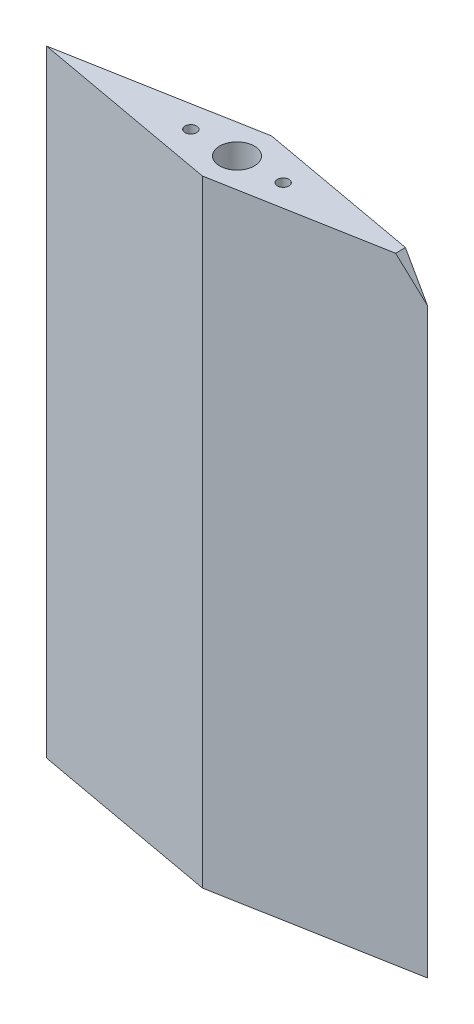
SolidWorks part; units mm, degrees
ref_plane "Front Plane" through (0, 0, 0) normal (0, 0, 1) x (1, 0, 0)
ref_plane "Top Plane" through (0, 0, 0) normal (0, 1, 0) x (1, 0, 0)
ref_plane "Right Plane" through (0, 0, 0) normal (1, 0, 0) x (0, 0, -1)
sketch "Sketch1" plane through (0, 0, 0) normal (0, 0, 1) x (1, 0, 0)
  line L0 (101.7924, 735.6565) -> (49.4049, 673.5573)
  line L1 (49.4049, 673.5573) -> (49.4049, 396.4974)
  line L2 (49.4049, 396.4974) -> (154.1799, 396.4974)
  line L3 (154.1799, 396.4974) -> (154.1799, 556.6364)
  line L4 (154.1799, 673.5573) -> (101.7924, 735.6565)
  line L5 (154.1799, 673.5573) -> (128.876, 673.5573)
  line L6 (128.876, 673.5573) -> (151.1488, 645.2298)
  line L7 (151.1488, 645.2298) -> (129.452, 645.2298)
  line L8 (129.452, 645.2298) -> (151.1488, 617.6349)
  line L9 (151.1488, 617.6349) -> (128.684, 617.6349)
  line L10 (128.684, 617.6349) -> (151.1488, 589.0632)
  line L11 (151.1488, 589.0632) -> (128.684, 589.0632)
  line L12 (128.684, 589.0632) -> (154.1799, 556.6364)
  point P2 (101.7924, 396.4974)
  dimension "D1" = 104.775
extrude "Boss-Extrude1" add sketch "Sketch1" along normal blind 9.525 and the other way blind 9.525
sketch "Sketch2" plane through (0, 396.4974, 0) normal (0, -1, 0) x (-1, 0, 0)
  line L0 (-49.4049, 0) -> (-101.7924, -9.525)
  line L1 (-49.4049, 9.525) -> (-49.4049, -9.525) construction
  line L2 (-49.4049, -9.525) -> (-154.1799, -9.525) construction
  line L3 (-101.7924, -9.525) -> (-154.1799, 0)
  line L4 (-154.1799, 9.525) -> (-154.1799, -9.525) construction
  line L5 (-154.1799, 0) -> (-159.6573, 0)
  line L6 (-159.6573, 0) -> (-159.6573, -13.6491)
  line L7 (-159.6573, -13.6491) -> (-44.1585, -13.6491)
  line L8 (-44.1585, -13.6491) -> (-44.1585, 0)
  line L9 (-44.1585, 0) -> (-49.4049, 0)
extrude "Cut-Extrude1" cut sketch "Sketch2" against normal through all
sketch "Sketch3" plane through (0, 396.4974, 0) normal (0, -1, 0) x (1, 0, 0)
  line L0 (49.4049, 0) -> (101.7924, -9.525)
  line L1 (101.7924, -9.525) -> (154.1799, 0)
  line L2 (154.1799, 0) -> (159.5806, 0)
  line L3 (159.5806, 0) -> (159.5806, -14.5007)
  line L4 (159.5806, -14.5007) -> (43.682, -14.5007)
  line L5 (43.682, -14.5007) -> (43.682, 0)
  line L6 (43.682, 0) -> (49.4049, 0)
extrude "Cut-Extrude2" cut sketch "Sketch3" against normal through all
sketch "Sketch4" plane through (4.9338, 0, 27.1357) normal (0.1789, 0, 0.9839) x (0.9839, 0, -0.1789)
  line L0 (98.4466, 735.6565) -> (98.4466, 396.4974) construction
  point P0 (98.4466, 678.5065)
  dimension "D1" = 57.15
ref_plane "Plane1" through (26.4305, 22.297, 133.782) normal (0.1913, 0.1614, 0.9682) x (0.9815, -0.0314, -0.1887)
sketch "Sketch5" plane through (26.4305, 22.297, 133.782) normal (0.1913, 0.1614, 0.9682) x (0.9815, -0.0314, -0.1887)
  line L1 (40.4892, 768.9526) -> (138.0076, 768.9526)
  line L2 (40.4892, 768.9526) -> (40.4892, 632.533)
  line L3 (40.4892, 632.533) -> (138.0076, 632.533)
  line L4 (138.0076, 768.9526) -> (138.0076, 632.533)
extrude "Cut-Extrude3" cut sketch "Sketch5" along normal through all
ref_plane "Plane2" through (-18.9819, 16.0133, 96.0799) normal (-0.1913, 0.1614, 0.9682) x (0.9815, 0.0314, 0.1887)
sketch "Sketch6" plane through (-18.9819, 16.0133, 96.0799) normal (-0.1913, 0.1614, 0.9682) x (0.9815, 0.0314, 0.1887)
  line L1 (61.3232, 620.6538) -> (136.4239, 620.6538)
  line L2 (61.3232, 620.6538) -> (61.3232, 774.9318)
  line L3 (61.3232, 774.9318) -> (136.4239, 774.9318)
  line L4 (136.4239, 620.6538) -> (136.4239, 774.9318)
extrude "Cut-Extrude4" cut sketch "Sketch6" along normal through all
mirror "Mirror1" about plane through (0, 0, 0) normal (0, 0, 1) of "Cut-Extrude4", "Cut-Extrude3"
sketch "Sketch7" plane through (0, 396.4974, 0) normal (0, -1, 0) x (1, 0, 0)
  circle A0 centre (101.7924, 0) radius 4.7625
  dimension "D1" = 9.525
extrude "Cut-Extrude5" cut sketch "Sketch7" against normal blind 254
sketch "Sketch8" plane through (0, 0, 0) normal (0, 0, 1) x (1, 0, 0)
  line L0 (-21.6446, 566.0769) -> (201.353, 566.0769)
  line L1 (101.7924, 735.6565) -> (101.7924, 396.4974)
  line L2 (49.4049, 396.4974) -> (101.7924, 396.4974) construction
  line L3 (-21.6446, 566.0769) -> (-21.6446, 762.3805)
  line L4 (-21.6446, 762.3805) -> (201.353, 762.3805)
  line L5 (201.353, 762.3805) -> (201.353, 566.0769)
  point P7 (101.7924, 566.0769)
extrude "Cut-Extrude6" cut sketch "Sketch8" against normal through all and the other way through all contours L5 L4 L3 L0 region at (89.8542, 664.2287, 0)
sketch "Sketch9" plane through (0, 566.0769, 0) normal (0, 1, 0) x (1, 0, 0)
  circle A0 centre (89.0924, 0) radius 1.5875
  circle A1 centre (114.4924, 0) radius 1.5875
  circle A2 centre (101.7924, 0) radius 4.7625 construction
  dimension "D1" = 12.7
  dimension "D2" = 12.7
  dimension "D3" = 3.175
extrude "Cut-Extrude7" cut sketch "Sketch9" against normal blind 12.7
sketch "Sketch10" plane through (0, 396.4974, 0) normal (0, -1, 0) x (1, 0, 0)
  circle A0 centre (89.0924, 0) radius 1.5875
  circle A1 centre (114.4924, 0) radius 1.5875
  circle A2 centre (101.7924, 0) radius 4.7625 construction
  dimension "D1" = 12.7
  dimension "D2" = 12.7
  dimension "D3" = 3.175
extrude "Cut-Extrude8" cut sketch "Sketch10" against normal blind 12.7
